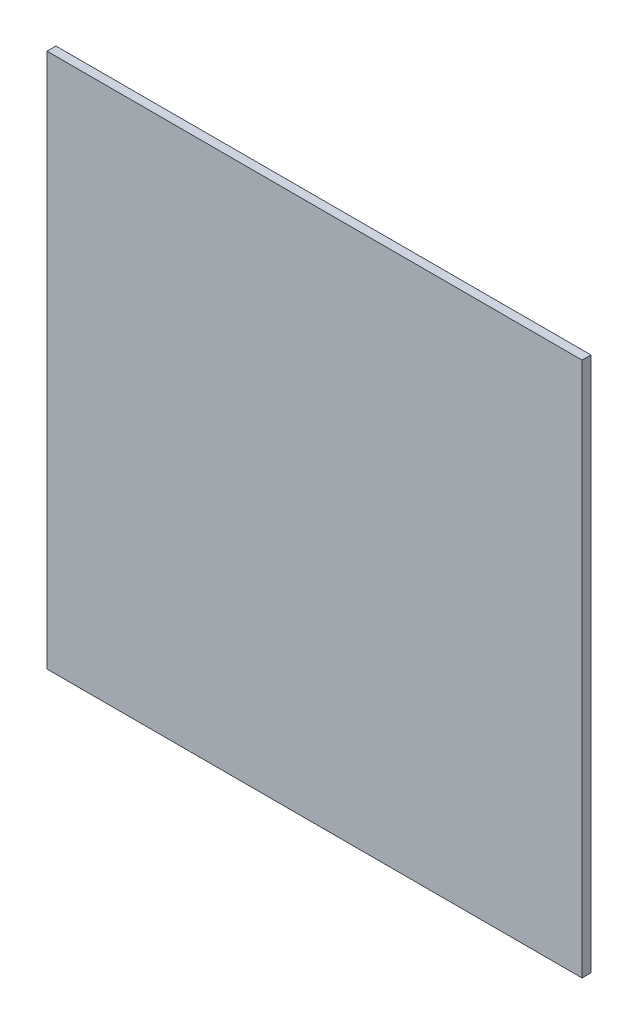
SolidWorks part; units mm, degrees
ref_plane "Front Plane" through (0, 0, 0) normal (0, 0, 1) x (1, 0, 0)
ref_plane "Top Plane" through (0, 0, 0) normal (0, 1, 0) x (1, 0, 0)
ref_plane "Right Plane" through (0, 0, 0) normal (1, 0, 0) x (0, 0, -1)
sketch "Sketch1" plane through (0, 0, 0) normal (0, 0, 1) x (1, 0, 0)
  line L1 (0, 0) -> (120000, 0)
  line L2 (0, 0) -> (0, 120000)
  line L3 (0, 120000) -> (120000, 120000)
  line L4 (120000, 0) -> (120000, 120000)
  dimension "D1" = 120000
  dimension "D2" = 120000
extrude "Boss-Extrude1" add sketch "Sketch1" along normal blind 2000
